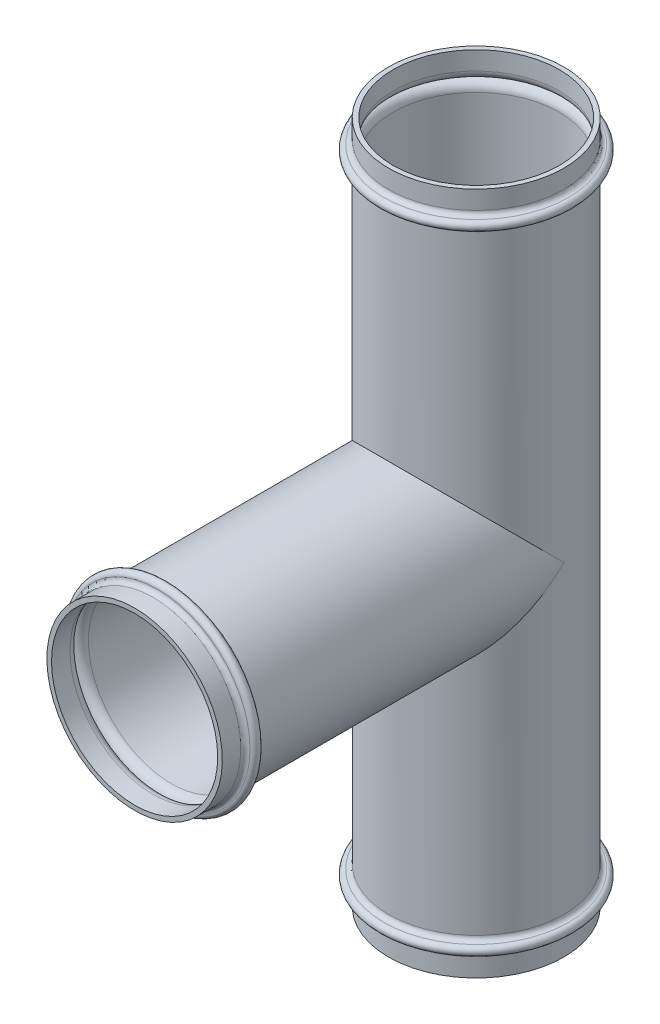
SolidWorks part; units mm, degrees
ref_plane "Ön Düzlem" through (0, 0, 0) normal (0, 0, 1) x (1, 0, 0)
ref_plane "Üst Düzlem" through (0, 0, 0) normal (0, 1, 0) x (1, 0, 0)
ref_plane "Sağ Düzlem" through (0, 0, 0) normal (1, 0, 0) x (0, 0, -1)
sketch "Sketch1" plane through (0, 0, 0) normal (0, 0, 1) x (1, 0, 0)
  line L0 (-21.206, -23.8015) -> (-21.206, 13.1985) construction
  line L1 (-21.206, 13.1985) -> (-11.706, 13.1985)
  line L2 (-11.706, 13.1985) -> (-11.706, 11.1985)
  line L3 (-21.206, -23.8015) -> (-11.706, -23.8015)
  line L4 (-11.706, -23.8015) -> (-11.706, 9.1985)
  line L5 (-10.706, 18.9133) -> (-10.706, 0) construction
  line L6 (-21.206, -23.8015) -> (-21.206, 13.1985)
  arc A0 (-11.706, 9.1985) -> (-11.206, 9.6985) centre (-11.206, 9.1985) cw
  arc A1 (-11.706, 11.1985) -> (-11.206, 10.6985) centre (-11.206, 11.1985) ccw
  arc A2 (-11.206, 10.6985) -> (-11.206, 9.6985) centre (-11.206, 10.1985) cw
  dimension "D1" = 1
revolve "Revolve1" add sketch "Sketch1" angle 360 about L6
ref_axis "Axis1" through (-59.7635, -23.8015, 0) along (1, 0, 0)
pattern_circular "CirPattern1" count 3 every 90 about axis through (-59.7635, -23.8015, 0) along (1, 0, 0) of "Revolve1"
shell "Shell1" thickness 0.5 removed face at (-21.206, -60.8015, 9.5) removed face at (-21.206, 13.1985, -9.5) removed face at (-21.206, -14.3015, 37)
